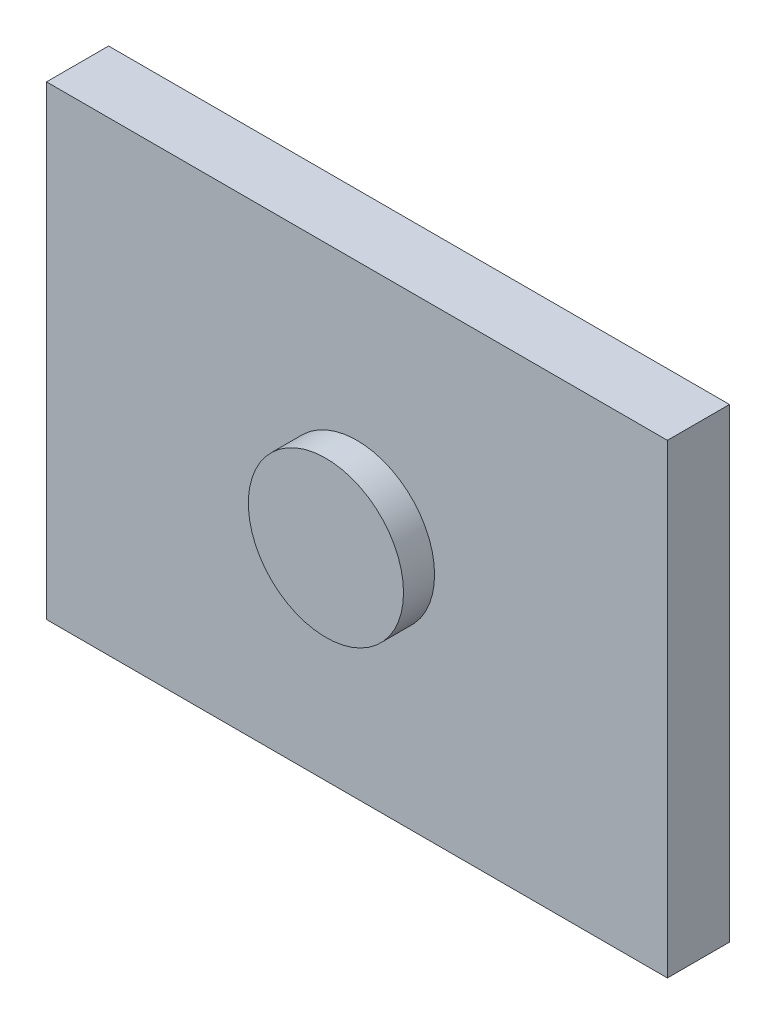
SolidWorks part; units mm, degrees
ref_plane "前视基准面" through (0, 0, 0) normal (0, 0, 1) x (1, 0, 0)
ref_plane "上视基准面" through (0, 0, 0) normal (0, 1, 0) x (1, 0, 0)
ref_plane "右视基准面" through (0, 0, 0) normal (1, 0, 0) x (0, 0, -1)
other "Configuration Table"
sketch "Sketch1" plane through (0, 0, 0) normal (0, 0, 1) x (1, 0, 0)
  line L1 (-100, -75) -> (100, -75)
  line L2 (-100, -75) -> (-100, 75)
  line L3 (-100, 75) -> (100, 75)
  line L4 (100, -75) -> (100, 75)
  line L5 (-100, -75) -> (100, 75) construction
  line L6 (-100, 75) -> (100, -75) construction
extrude "Boss-Extrude1" add sketch "Sketch1" along normal blind 20
ref_plane "Plane1" through (0, 0, 20) normal (0, 0, 1) x (1, 0, 0)
sketch "Sketch2" plane through (0, 0, 20) normal (0, 0, 1) x (1, 0, 0)
  circle A0 centre (0, 0) radius 25
extrude "Boss-Extrude2" add sketch "Sketch2" along normal blind 10
sketch3d "3DSketch1"
  line L0 (0, 0, 0) -> (0, 0, 1000) construction
ref_axis "AXIS_J1_Z" through (0, 0, 0) along (0, 0, 1)
ref_plane "PL_BASE_TOP" through (0, 0, 20) normal (0, 0, 1) x (1, 0, 0)
ref_plane "PL_BASE_ZERO_XZ" through (0, 0, 0) normal (0, 1, 0) x (1, 0, 0)
